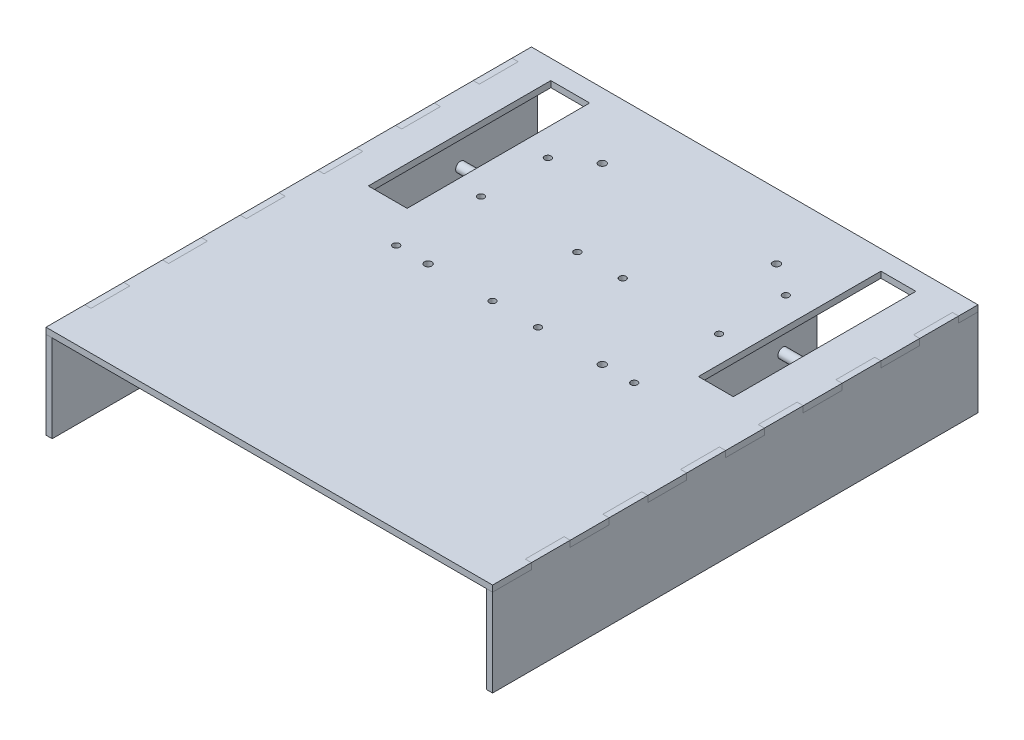
SolidWorks part; units mm, degrees
ref_plane "Front Plane" through (0, 0, 0) normal (0, 0, 1) x (1, 0, 0)
ref_plane "Top Plane" through (0, 0, 0) normal (0, 1, 0) x (1, 0, 0)
ref_plane "Right Plane" through (0, 0, 0) normal (1, 0, 0) x (0, 0, -1)
sketch "Sketch2" plane through (0, 0, 0) normal (0, 1, 0) x (1, 0, 0)
  line L7 (-172.2662, -88.2141) -> (57.7338, -88.2141)
  line L8 (17.7338, 151.7859) -> (35.7338, 151.7859)
  line L9 (57.7338, -88.2141) -> (57.7338, -68.2141)
  line L10 (57.7338, -68.2141) -> (54.5588, -68.2141)
  line L11 (54.5588, -68.2141) -> (54.5588, -48.2141)
  line L12 (54.5588, -48.2141) -> (57.7338, -48.2141)
  line L13 (-172.2662, -88.2141) -> (-172.2662, -68.2141)
  line L14 (-172.2662, -68.2141) -> (-169.0912, -68.2141)
  line L15 (-169.0912, -68.2141) -> (-169.0912, -48.2141)
  line L16 (-169.0912, -48.2141) -> (-172.2662, -48.2141)
  line L17 (-172.2662, -48.2141) -> (-172.2662, -28.2141)
  line L18 (-172.2662, -28.2141) -> (-169.0912, -28.2141)
  line L19 (-169.0912, -28.2141) -> (-169.0912, -8.2141)
  line L20 (-169.0912, -8.2141) -> (-172.2662, -8.2141)
  line L21 (57.7338, -28.2141) -> (54.5588, -28.2141)
  line L22 (54.5588, -28.2141) -> (54.5588, -8.2141)
  line L23 (54.5588, -8.2141) -> (57.7338, -8.2141)
  line L24 (57.7338, -48.2141) -> (57.7338, -28.2141)
  line L25 (-172.2662, -8.2141) -> (-172.2662, 11.7859)
  line L26 (-172.2662, 11.7859) -> (-169.0912, 11.7859)
  line L27 (-169.0912, 11.7859) -> (-169.0912, 31.7859)
  line L28 (-169.0912, 31.7859) -> (-172.2662, 31.7859)
  line L29 (57.7338, 11.7859) -> (54.5588, 11.7859)
  line L30 (54.5588, 11.7859) -> (54.5588, 31.7859)
  line L31 (54.5588, 31.7859) -> (57.7338, 31.7859)
  line L32 (57.7338, -8.2141) -> (57.7338, 11.7859)
  line L33 (-172.2662, 31.7859) -> (-172.2662, 51.7859)
  line L34 (-172.2662, 51.7859) -> (-169.0912, 51.7859)
  line L35 (-169.0912, 51.7859) -> (-169.0912, 71.7859)
  line L36 (-169.0912, 71.7859) -> (-172.2662, 71.7859)
  line L37 (57.7338, 51.7859) -> (54.5588, 51.7859)
  line L38 (54.5588, 51.7859) -> (54.5588, 71.7859)
  line L39 (54.5588, 71.7859) -> (57.7338, 71.7859)
  line L40 (57.7338, 31.7859) -> (57.7338, 51.7859)
  line L45 (17.7338, 151.7859) -> (17.7338, 57.7859)
  line L46 (17.7338, 57.7859) -> (35.7338, 57.7859)
  line L47 (35.7338, 151.7859) -> (35.7338, 57.7859)
  line L48 (-152.2662, 151.7859) -> (-132.2662, 151.7859)
  line L49 (-152.2662, 151.7859) -> (-152.2662, 57.7859)
  line L50 (-152.2662, 57.7859) -> (-132.2662, 57.7859)
  line L51 (-132.2662, 151.7859) -> (-132.2662, 57.7859)
  line L52 (-172.2662, 71.7859) -> (-172.2662, 91.7859)
  line L53 (-172.2662, 91.7859) -> (-169.0912, 91.7859)
  line L54 (-169.0912, 91.7859) -> (-169.0912, 111.7859)
  line L55 (-169.0912, 111.7859) -> (-172.2662, 111.7859)
  line L56 (57.7338, 91.7859) -> (54.5588, 91.7859)
  line L57 (54.5588, 91.7859) -> (54.5588, 111.7859)
  line L58 (54.5588, 111.7859) -> (57.7338, 111.7859)
  line L59 (57.7338, 71.7859) -> (57.7338, 91.7859)
  line L63 (-172.2662, 111.7859) -> (-172.2662, 131.7859)
  line L64 (-172.2662, 131.7859) -> (-169.0912, 131.7859)
  line L65 (-169.0912, 131.7859) -> (-169.0912, 151.7859)
  line L66 (-169.0912, 151.7859) -> (-172.2662, 151.7859)
  line L67 (57.7338, 131.7859) -> (54.5588, 131.7859)
  line L68 (54.5588, 131.7859) -> (54.5588, 151.7859)
  line L69 (54.5588, 151.7859) -> (57.7338, 151.7859)
  line L70 (57.7338, 111.7859) -> (57.7338, 131.7859)
  line L71 (57.7338, 151.7859) -> (57.7338, 161.7859)
  line L72 (57.7338, 161.7859) -> (-172.2662, 161.7859)
  line L73 (-172.2662, 161.7859) -> (-172.2662, 151.7859)
  dimension "D1" = 3.175
  dimension "D2" = 20
  dimension "D3" = 20
  dimension "D4" = 3.175
  dimension "D6" = 230
  dimension "D8" = 18
  dimension "D9" = 20
  dimension "D10" = 22
  dimension "D11" = 20
  dimension "D13" = 94
  dimension "D7" = 10
  dimension "D12" = 10
  dimension "D5" = 6
extrude "Boss-Extrude1" add sketch "Sketch2" along normal blind 3.175
ref_plane "Plane3" through (-57.2662, 0, 0) normal (-1, 0, 0) x (0, 0, 1)
sketch "Sketch3" plane through (-169.0912, 0, 0) normal (-1, 0, 0) x (0, 0, 1)
  line L0 (68.2141, 3.175) -> (68.2141, 0)
  line L1 (68.2141, 0) -> (88.2141, 0)
  line L2 (88.2141, 0) -> (88.2141, -45)
  line L3 (68.2141, 3.175) -> (48.2141, 3.175)
  line L4 (48.2141, 3.175) -> (48.2141, 0)
  line L5 (48.2141, 0) -> (28.2141, 0)
  line L6 (28.2141, 0) -> (28.2141, 3.175)
  line L7 (28.2141, 3.175) -> (8.2141, 3.175)
  line L8 (8.2141, 3.175) -> (8.2141, 0)
  line L9 (8.2141, 0) -> (-11.7859, 0)
  line L10 (-11.7859, 0) -> (-11.7859, 3.175)
  line L11 (-91.7859, 0) -> (-91.7859, 3.175)
  line L12 (-11.7859, 3.175) -> (-31.7859, 3.175)
  line L13 (-31.7859, 3.175) -> (-31.7859, 0)
  line L14 (-31.7859, 0) -> (-51.7859, 0)
  line L15 (-51.7859, 0) -> (-51.7859, 3.175)
  line L16 (-51.7859, 3.175) -> (-71.7859, 3.175)
  line L17 (-71.7859, 3.175) -> (-71.7859, 0)
  line L18 (-71.7859, 0) -> (-91.7859, 0)
  line L21 (-91.7859, 3.175) -> (-111.7859, 3.175)
  line L22 (-111.7859, 3.175) -> (-111.7859, 0)
  line L25 (-111.7859, 0) -> (-131.7859, 0)
  line L26 (-151.7859, 0) -> (-131.7859, 0) construction
  line L27 (-131.7859, 3.175) -> (-131.7859, 0) construction
  line L28 (-131.7859, 0) -> (-131.7859, 3.175)
  line L29 (-131.7859, 3.175) -> (-151.7859, 3.175)
  line L30 (-151.7859, 3.175) -> (-151.7859, 0)
  line L31 (-151.7859, 3.175) -> (-151.7859, 0) construction
  line L32 (-151.7859, 0) -> (-161.732, 0)
  line L33 (-161.732, 0) -> (-161.732, -45)
  line L34 (-161.732, -45) -> (88.2141, -45)
extrude "Boss-Extrude2" add sketch "Sketch3" along normal blind 3.175 separate body
sketch "Sketch4" plane through (0, 0, 0) normal (0, -1, 0) x (1, 0, 0)
  line L0 (-128.2662, -122.8126) -> (-128.2662, -33.5103)
  line L1 (-128.2662, -122.8126) -> (-110.4256, -122.8126)
  line L2 (-128.2662, -33.5103) -> (-110.4287, -33.5103)
  line L5 (-64.765, -32.9867) -> (-64.765, -87.1773)
  line L6 (-64.765, -32.9867) -> (-73.1795, -32.9867)
  line L7 (-64.765, -87.1773) -> (-73.1795, -87.1773)
  line L9 (-110.4287, -33.5103) -> (-110.4287, -55.4044)
  line L10 (-110.4287, -55.4044) -> (-73.1795, -55.4044)
  line L11 (-73.1795, -55.4044) -> (-73.1795, -32.9867)
  line L12 (-73.1795, -87.1773) -> (-73.1795, -65.4044)
  line L13 (-73.1795, -65.4044) -> (-110.4256, -65.4044)
  line L14 (-110.4256, -65.4044) -> (-110.4256, -122.8126)
extrude "Boss-Extrude3" add sketch "Sketch4" along normal blind 1.6129 separate body
sketch "Sketch6" plane through (-128.2662, 113.8349, 0) normal (1, 0, 0) x (0, -1, 0)
  line L0 (115.4478, 33.5103) -> (113.8349, 33.5103)
  line L1 (113.8349, 33.5103) -> (113.8349, 122.8126)
  line L4 (133.4041, 33.5103) -> (115.4478, 33.5103)
  line L7 (135.755, 122.8126) -> (113.8349, 122.8126)
  line L8 (113.8349, 57.7859) -> (113.8349, 151.7859) construction
  line L10 (115.4478, 122.8126) -> (113.8349, 122.8126) construction
  line L11 (135.755, 122.8126) -> (135.755, 87.3557)
  circle A2 centre (133.4041, 73.86) radius 1.27
  circle A4 centre (133.4041, 51.6858) radius 2.3749
  circle A5 centre (125.8349, 105.2548) radius 2.55
  circle A6 centre (123.1933, 51.6858) radius 1.27
  circle A8 centre (143.6149, 51.6858) radius 1.27
  arc A10 (135.755, 87.3557) -> (133.4041, 33.5103) centre (121.4093, 61.008) cw
  line M25 (113.8349, 33.5103) -> (113.8349, 122.8126)
  line M26 (113.8349, 122.8126) -> (115.4478, 122.8126)
  line M27 (115.4478, 122.8126) -> (115.4478, 33.5103)
  line M28 (115.4478, 33.5103) -> (113.8349, 33.5103)
  dimension "D1" = 5.1
  dimension "D2" = 12
extrude "Boss-Extrude4" add sketch "Sketch6" along normal blind 1.6129 contours M28 M25 M26 M27 | L4 M27 | A6 A2 A4 A8 region at (-128.2662, -15.7988, -73.9814) region at (-128.2662, -0.8065, -78.1615)
sketch "Sketch7" plane through (0, -1.6129, 0) normal (0, -1, 0) x (1, 0, 0)
  circle A0 centre (-118.541, -82.125) radius 1.7
  circle A1 centre (-118.541, -38.4299) radius 1.7
  circle A2 centre (-68.9723, -38.4299) radius 1.7
  circle A3 centre (-68.9723, -82.125) radius 1.7
  circle A4 centre (-118.541, -116.5476) radius 1.7
  circle A5 centre (-102.1184, -38.4299) radius 1.9
  circle A6 centre (-102.1184, -128.1299) radius 1.9
  dimension "D3" = 3.4
  dimension "D4" = 3.4
  dimension "D5" = 3.4
  dimension "D6" = 3.4
  dimension "D1" = 3.4
  dimension "D2" = 3.8
  dimension "D8" = 3.8
  dimension "D7" = 89.7
extrude "Cut-Extrude1" cut sketch "Sketch7" against normal blind 10
mirror "Mirror1" about plane through (-57.2662, 0, 0) normal (-1, 0, 0) of bodies 157 103 158
mirror "Mirror2" about plane through (-57.2662, 0, 0) normal (-1, 0, 0) of "Cut-Extrude1"
sketch "Sketch9" plane through (-152.2662, 0, 0) normal (1, 0, 0) x (0, 0, -1)
  circle A0 centre (105.2548, -12) radius 2.5
extrude "Boss-Extrude6" add sketch "Sketch9" along normal blind 189 separate body
equation "\"hardboard_width\"= 3.175"
equation "\"D1@Boss-Extrude1\"=\"hardboard_width\""
equation "\"D1@Sketch2\"=\"hardboard_width\""
equation "\"D4@Sketch2\"=\"hardboard_width\""
equation "\"D1@Boss-Extrude2\"=\"hardboard_width\""
equation "\"steel_24g_thickness\"= 0.5"
equation "\"m3_clearance_hole\"= 3.4"
equation "\"D3@Sketch7\"=\"m3_clearance_hole\""
equation "\"D4@Sketch7\"=\"m3_clearance_hole\""
equation "\"D5@Sketch7\"=\"m3_clearance_hole\""
equation "\"D6@Sketch7\"=\"m3_clearance_hole\""
equation "\"steel_16g_thickness\"=1.6129"
equation "\"D1@Boss-Extrude3\"=\"steel_16g_thickness\""
equation "\"D1@Boss-Extrude4\"=\"steel_16g_thickness\""
equation "\"D1@Sketch7\"=\"m3_clearance_hole\""
